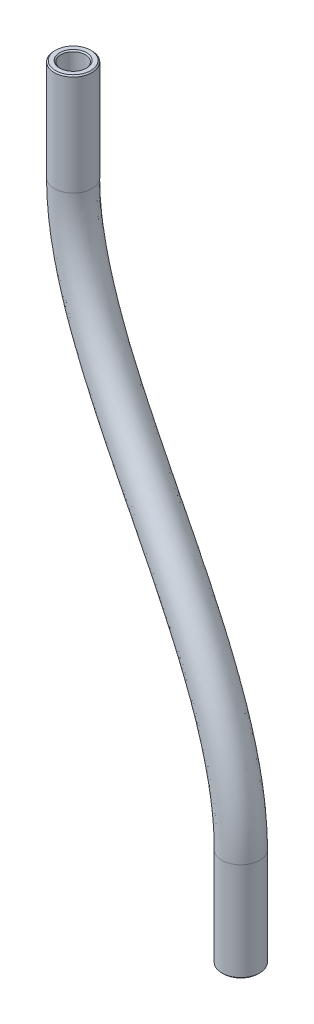
SolidWorks part; units mm, degrees
ref_plane "Front Plane" through (0, 0, 0) normal (0, 0, 1) x (1, 0, 0)
ref_plane "Top Plane" through (0, 0, 0) normal (0, 1, 0) x (1, 0, 0)
ref_plane "Right Plane" through (0, 0, 0) normal (1, 0, 0) x (0, 0, -1)
sketch3d "3DSketch1"
  line L0 (-150.0853, -92.9823, 33.525) -> (-150.0853, -103.4823, 33.525)
  line L1 (-174.4237, -35.8, 27.0017) -> (-174.4237, -46.6, 27.0017)
  spline S0 degree 3 poles (-174.4237, -46.6, 27.0017) (-174.4237, -55.016, 27.0017) (-162.2545, -69.4599, 30.2634) (-150.0853, -83.694, 33.525) (-150.0853, -92.9823, 33.525) knots 0 0 0 0 0.478322 1 1 1 1
sketch "Sketch1" plane through (0, -95.3823, 0) normal (0, 1, 0) x (1, 0, 0)
  circle A0 centre (-150.0853, -33.525) radius 2
  circle A2 centre (-150.0853, -33.525) radius 3.8416 construction
  circle A3 centre (-150.0853, -33.525) radius 1.3
  dimension "D1" = 4
  dimension "D2" = 2.6
sweep "Sweep1" add profiles "Sketch1" path "3DSketch1"
chamfer "Chamfer1" distance 0.127 angle 45 4 edges at (-176.4237, -35.8, 27.0017) (-175.7237, -35.8, 27.0017) (-152.0853, -103.4823, 33.525) (-151.3853, -103.4823, 33.525)
